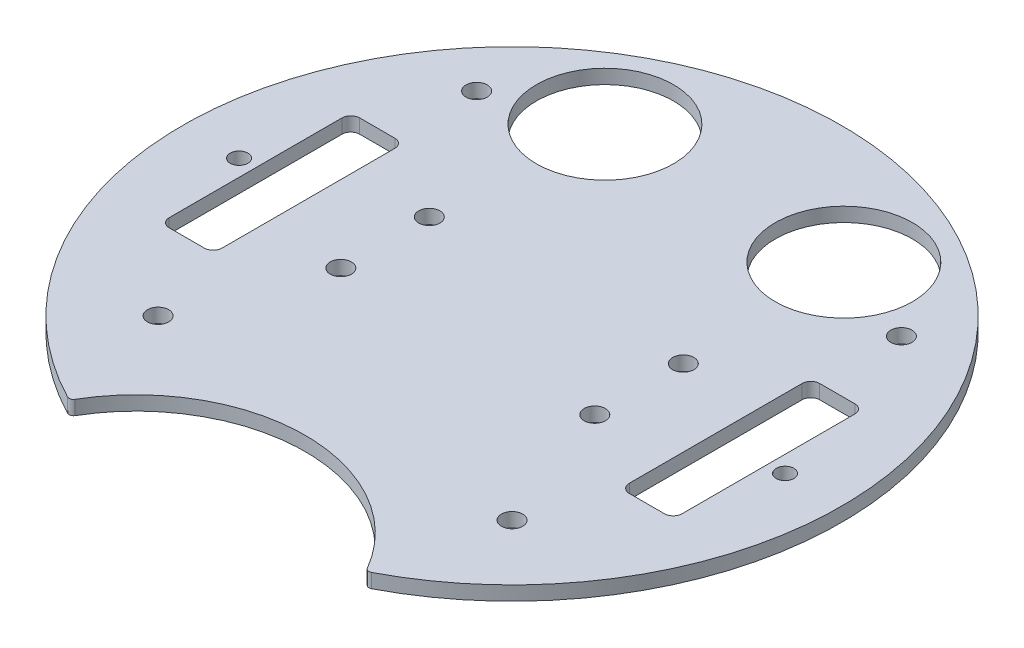
SolidWorks part; units mm, degrees
material "Plain Carbon Steel"
ref_plane "Front Plane" through (0, 0, 0) normal (0, 0, 1) x (1, 0, 0)
ref_plane "Top Plane" through (0, 0, 0) normal (0, 1, 0) x (1, 0, 0)
ref_plane "Right Plane" through (0, 0, 0) normal (1, 0, 0) x (0, 0, -1)
sketch "Sketch1" plane through (0, 0, 0) normal (0, 1, 0) x (1, 0, 0)
  line L1 (0, -85) -> (0, 0) construction
  arc A0 (34.3603, -66.1031) -> (-34.3603, -66.1031) centre (0, 0) ccw
  arc A1 (33.0354, -65.7199) -> (-33.0354, -65.7199) centre (0, -85) ccw
  arc A2 (34.3603, -66.1031) -> (33.0354, -65.7199) centre (33.8991, -65.2158) cw
  arc A3 (-33.0354, -65.7199) -> (-34.3603, -66.1031) centre (-33.8991, -65.2158) cw
  dimension "D1" = 149
  dimension "D2" = 76.5
  dimension "D4" = 1
  dimension "D3" = 85
extrude "Boss-Extrude1" add sketch "Sketch1" along normal blind 3.2
sketch "solenoid placement" plane through (0, 3.2, 0) normal (0, 1, 0) x (1, 0, 0)
  line L0 (0, 0) -> (0, -36) construction
  line L1 (0, -36) -> (0, -46.75) construction
  line L2 (-19, -36) -> (19, -36)
  line L3 (-19, -36) -> (-19, 28)
  line L4 (-19, 28) -> (19, 28)
  line L5 (19, -36) -> (19, 28)
  circle A1 centre (0, 0) radius 74.5 construction
  arc A2 (34.3603, -66.1031) -> (-34.3603, -66.1031) centre (0, 0) ccw construction
  arc A3 (33.0354, -65.7199) -> (-33.0354, -65.7199) centre (0, -85) ccw construction
  dimension "D1" = 64
  dimension "D2" = 36
  dimension "D4" = 38
sketch "Sketch2" plane through (0, 3.2, 0) normal (0, 1, 0) x (1, 0, 0)
  line L1 (-57.07, 20.6344) -> (-46.91, 20.6344) construction
  line L2 (-57.07, 20.6344) -> (-57.07, -20.6344) construction
  line L3 (-57.07, -20.6344) -> (-46.91, -20.6344) construction
  line L4 (-46.91, 20.6344) -> (-46.91, -20.6344) construction
  line L8 (-57.37, -20.9344) -> (-46.61, -20.9344)
  line L9 (-46.61, 20.9344) -> (-46.61, -20.9344)
  line L10 (-57.37, 20.9344) -> (-46.61, 20.9344)
  line L11 (-57.37, 20.9344) -> (-57.37, -20.9344)
  line L12 (0, 0) -> (0, 74.5) construction
  line L13 (46.91, 20.6344) -> (46.91, -20.6344) construction
  line L14 (57.07, -20.6344) -> (46.91, -20.6344) construction
  line L15 (57.07, 20.6344) -> (57.07, -20.6344) construction
  line L16 (57.07, 20.6344) -> (46.91, 20.6344) construction
  line L17 (57.37, 20.9344) -> (57.37, -20.9344)
  line L18 (57.37, 20.9344) -> (46.61, 20.9344)
  line L19 (46.61, 20.9344) -> (46.61, -20.9344)
  line L20 (57.37, -20.9344) -> (46.61, -20.9344)
  arc A0 (34.3603, -66.1031) -> (-34.3603, -66.1031) centre (0, 0) ccw construction
extrude "Cut-Extrude1" cut sketch "Sketch2" against normal through all
sketch "Sketch3" plane through (0, 0, 0) normal (0, -1, 0) x (1, 0, 0)
  line L0 (0, 0) -> (0, -74.5) construction
  circle A0 centre (-61.7, 0) radius 2
  circle A1 centre (-28.7007, 10) radius 2.4
  circle A2 centre (-28.7007, -10) radius 2.4
  arc A3 (-34.3603, 66.1031) -> (34.3603, 66.1031) centre (0, 0) ccw construction
  circle A4 centre (28.7007, -10) radius 2.4
  circle A5 centre (28.7007, 10) radius 2.4
  circle A6 centre (61.7, 0) radius 2
  dimension "D1" = 4
  dimension "D2" = 4.8
extrude "Cut-Extrude2" cut sketch "Sketch3" against normal through all
sketch "Sketch4" plane through (0, 3.2, 0) normal (0, 1, 0) x (1, 0, 0)
  line L0 (0, 0) -> (0, 74.5) construction
  line L1 (0, 48) -> (-27, 48) construction
  circle A0 centre (-27, 48) radius 15
  arc A1 (34.3603, -66.1031) -> (-34.3603, -66.1031) centre (0, 0) ccw construction
  circle A2 centre (27, 48) radius 15
  dimension "D1" = 30
  dimension "D2" = 48
  dimension "D3" = 27
extrude "Cut-Extrude3" cut sketch "Sketch4" against normal through all
sketch "Sketch5" plane through (0, 3.2, 0) normal (0, 1, 0) x (1, 0, 0)
  line L0 (0, 0) -> (0, 74.5) construction
  line L1 (-55.9558, 21.5201) -> (-48.0242, 21.5201)
  line L2 (-57.9558, 19.5201) -> (-57.9558, -19.5201)
  line L3 (-55.9558, -21.5201) -> (-48.0242, -21.5201)
  line L4 (-46.0242, 19.5201) -> (-46.0242, -19.5201)
  line L5 (46.0242, 19.5201) -> (46.0242, -19.5201)
  line L6 (55.9558, -21.5201) -> (48.0242, -21.5201)
  line L7 (57.9558, 19.5201) -> (57.9558, -19.5201)
  line L8 (55.9558, 21.5201) -> (48.0242, 21.5201)
  arc A0 (-57.9558, -19.5201) -> (-55.9558, -21.5201) centre (-55.9558, -19.5201) ccw
  arc A1 (-48.0242, -21.5201) -> (-46.0242, -19.5201) centre (-48.0242, -19.5201) ccw
  arc A2 (-48.0242, 21.5201) -> (-46.0242, 19.5201) centre (-48.0242, 19.5201) cw
  arc A3 (-55.9558, 21.5201) -> (-57.9558, 19.5201) centre (-55.9558, 19.5201) ccw
  arc A4 (34.3603, -66.1031) -> (-34.3603, -66.1031) centre (0, 0) ccw construction
  arc A5 (55.9558, 21.5201) -> (57.9558, 19.5201) centre (55.9558, 19.5201) cw
  arc A6 (48.0242, 21.5201) -> (46.0242, 19.5201) centre (48.0242, 19.5201) ccw
  arc A7 (48.0242, -21.5201) -> (46.0242, -19.5201) centre (48.0242, -19.5201) cw
  arc A8 (57.9558, -19.5201) -> (55.9558, -21.5201) centre (55.9558, -19.5201) cw
  point P15 (-57.37, 20.9344)
  dimension "D1" = 2
extrude "Cut-Extrude4" cut sketch "Sketch5" against normal through all
sketch "Sketch6" plane through (0, 3.2, 0) normal (0, 1, 0) x (1, 0, 0)
  line L0 (0, 74.5) -> (0, -46.75) construction
  circle A0 centre (48, 40) radius 2.4
  circle A1 centre (-40, -40) radius 2.4
  arc A4 (34.3603, -66.1031) -> (-34.3603, -66.1031) centre (0, 0) ccw construction
  arc A5 (33.0354, -65.7199) -> (-33.0354, -65.7199) centre (0, -85) ccw construction
  circle A6 centre (40, -40) radius 2.4
  circle A7 centre (-48, 40) radius 2.4
  dimension "D3" = 4.8
  dimension "D1" = 40
  dimension "D2" = 40
  dimension "D4" = 48
  dimension "D5" = 40
extrude "Cut-Extrude5" cut sketch "Sketch6" against normal through all
chamfer "Chamfer1" [suppressed] distance 2 angle 41
sketch "Sketch8" plane through (0, 3.2, 0) normal (0, 1, 0) x (1, 0, 0)
  circle A0 centre (-27, 48) radius 15.5
  circle A1 centre (27, 48) radius 15.5
  dimension "D1" = 31
extrude "Cut-Extrude6" cut sketch "Sketch8" against normal through all
equation "\"smallPulleyTeeth\"= 15"
equation "\"largePulleyTeeth\"= 30"
equation "\"eighthThick\"= 2.9mm"
equation "\"sixteenthThick\" = 1.7mm"
equation "\"quarterThick\"=6.0mm"
equation "\"OD\" = 145mm"
equation "\"puckAngle\" = 60.5deg"
equation "\"puckDiam\" = 76.5mm"
equation "\"D2@Sketch1\"=\"puckDiam\""
equation "\"D1@Boss-Extrude1\"=\"eighthThick\""
equation "\"axlePress\" = 5.9mm"
equation "\"press\" = 0.2mm"
equation "\"wheelClear\" = 0.3mm"
equation "\"D1@Sketch2\"=\"wheelClear\""
equation "\"10-32clear\" = 4.8mm"
equation "\"6-32clear\" = 3.3mm"
equation "\"8-32clear\" = 4.0mm"
equation "\"wheelHeight\" = 22mm"
equation "\"D1@Sketch3\"=\"8-32clear\""
equation "\"D2@Sketch3\"=\"10-32clear\""
equation "\"D3@Sketch6\"=\"10-32clear\""
equation "\"puckDist\" = 85mm"
equation "\"4-40clear\" = 3.0mm"
equation "\"wheelWell\" = 65mm"
equation "\"D3@Sketch1\"=\"puckDist\""
